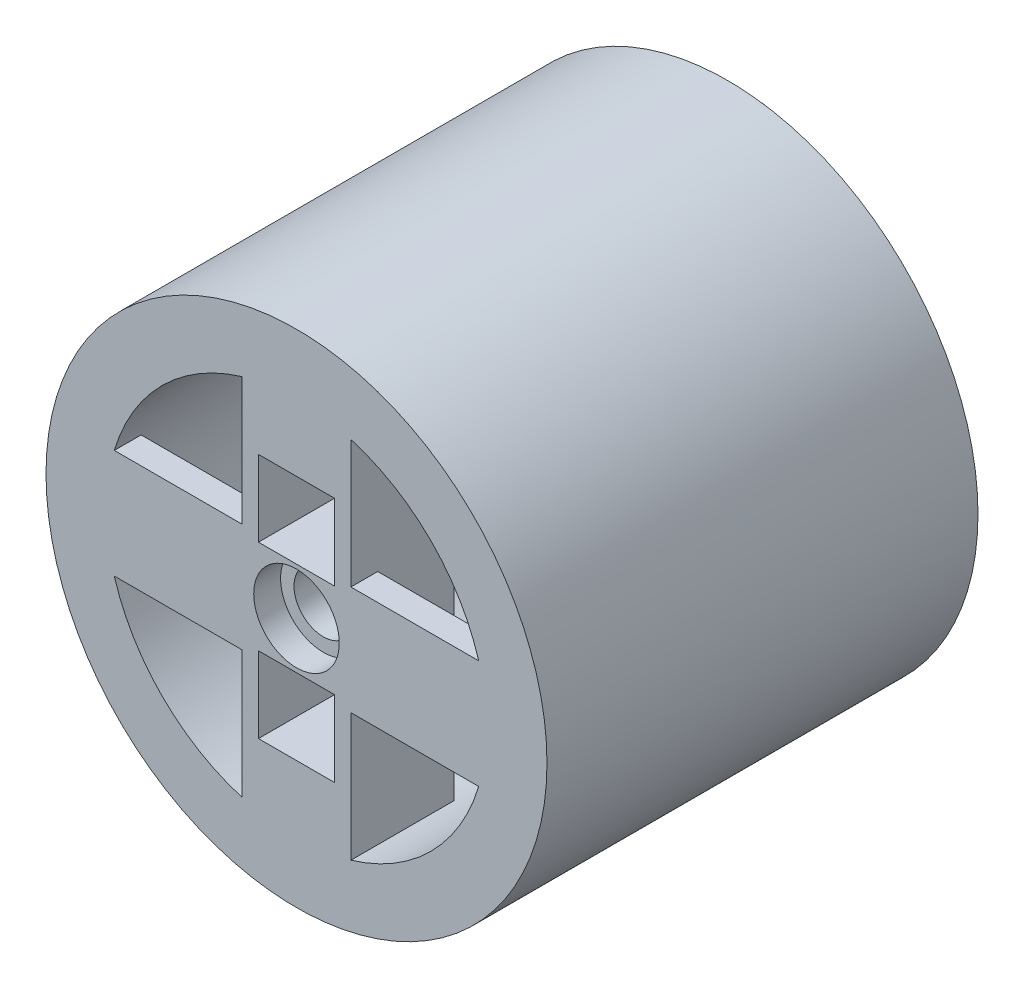
SolidWorks part; units mm, degrees
ref_plane "Front Plane" through (0, 0, 0) normal (0, 0, 1) x (1, 0, 0)
ref_plane "Top Plane" through (0, 0, 0) normal (0, 1, 0) x (1, 0, 0)
ref_plane "Right Plane" through (0, 0, 0) normal (1, 0, 0) x (0, 0, -1)
sketch "Sketch1" plane through (0, 0, 0) normal (0, 0, 1) x (1, 0, 0)
  line L0 (23.5, 0) -> (22.5, 0)
  line L1 (0, 25.15) -> (0, 22.5)
  line L3 (0, -22.5) -> (0, -29.64)
  line L4 (22.5, 0) -> (-22.5, 0)
  line L8 (28.3, 4.9) -> (23.5, 4.9)
  line L9 (28.3, 4.9) -> (28.3, -4.9)
  line L10 (28.3, -4.9) -> (23.5, -4.9)
  line L11 (23.5, 4.9) -> (23.5, -4.9)
  line L24 (-2.85, 27.85) -> (-2.85, 25.15)
  line L25 (-2.85, 27.85) -> (2.85, 27.85)
  line L26 (2.85, 27.85) -> (2.85, 25.15)
  line L27 (-2.85, 25.15) -> (2.85, 25.15)
  circle A0 centre (0, 0) radius 22.5
  circle A1 centre (0, 0) radius 29.64
  point P0 (0, 25.15)
  point P1 (23.5, 0)
  dimension "D3" = 5.7
  dimension "D1" = 1
  dimension "D2" = 2.65
  dimension "D4" = 2.7
extrude "Boss-Extrude1" add sketch "Sketch1" along normal blind 51 contours A1 L11 L8 L9 L10 L27 L24 L25 L26 A0 | L24 L27 L26 L25 | L8 L11 L10 L9 | L3 A1 L9 L10 L11 L0 A0 region at (-20.3658, 20.3658, 0) region at (0, 26.5, 0) region at (25.9, 0, 0)
extrude "Boss-Extrude2" add sketch "Sketch1<4>" against normal blind 1.5 contours L25 L26 L27 L24
sketch "Sketch1<4>" plane through (0, 0, 0) normal (0, 0, 1) x (1, 0, 0) same geometry as "Sketch1"
sketch "Sketch3" plane through (0, 0, 0) normal (0, 1, 0) x (1, 0, 0)
  line L0 (0, -26.5014) -> (0, 0)
pattern_circular "CirPattern2" count 3 over 360 about axis through (0, 0, 26.5014) along (0, 0, -1) of "Boss-Extrude2" reverse direction yes
sketch "Sketch4" plane through (0, 0, 51) normal (0, 0, 1) x (1, 0, 0)
  line L1 (6.4367, -24.2141) -> (-6.4367, -24.2141)
  line L2 (6.4367, -24.2141) -> (6.4367, 24.2141)
  line L3 (6.4367, 24.2141) -> (-6.4367, 24.2141)
  line L4 (-6.4367, -24.2141) -> (-6.4367, 24.2141)
  line L5 (6.4367, -24.2141) -> (-6.4367, 24.2141) construction
  line L6 (6.4367, 24.2141) -> (-6.4367, -24.2141) construction
  line L7 (-24.2141, 6.4367) -> (24.2141, 6.4367)
  line L8 (-24.2141, 6.4367) -> (-24.2141, -6.4367)
  line L9 (-24.2141, -6.4367) -> (24.2141, -6.4367)
  line L10 (24.2141, 6.4367) -> (24.2141, -6.4367)
  line L11 (-24.2141, 6.4367) -> (24.2141, -6.4367) construction
  line L12 (-24.2141, -6.4367) -> (24.2141, 6.4367) construction
  point P0 (0, 0)
  point P5 (0, 0)
  point P11 (6.4367, 24.2141)
  circle M5 centre (0, 0) radius 22.5
extrude "Boss-Extrude3" add sketch "Sketch4" against normal blind 3.175 contours L2 L9 L7 M5 | L9 L4 L2 M5 | L9 L10 L7 L8 | L2 L3 L4 L1 region at (0, -14.3154, 51) region at (14.3154, 0, 51)
sketch "Sketch7" plane through (0, 0, 51) normal (0, 0, 1) x (1, 0, 0)
  circle A0 centre (0, 0) radius 5.0625
extrude "Cut-Extrude2" cut sketch "Sketch7" against normal up to next and the other way through all
sketch "Sketch8" plane through (0, 0, 47.825) normal (0, 0, 1) x (1, 0, 0)
  line L0 (0, -3.475) -> (0, -24.0864)
  line L5 (6.4367, 24.0864) -> (-6.4367, 24.0864)
  line L6 (6.4367, 24.0864) -> (6.4367, -24.0864)
  line L11 (6.4367, -24.0864) -> (-6.4367, -24.0864)
  line L12 (-6.4367, 24.0864) -> (-6.4367, -24.0864)
  line L13 (6.4367, 24.0864) -> (-6.4367, -24.0864) construction
  line L14 (6.4367, -24.0864) -> (-6.4367, 24.0864) construction
  line L15 (6.4367, 6.4367) -> (6.4367, 21.5597) construction
  circle A1 centre (0, 0) radius 3.475
  point P0 (0, 0)
  dimension "D2" = 12.8734
extrude "Boss-Extrude4" add sketch "Sketch8" against normal blind 9 contours L5 L12 L11 L6 | A1
extrude "Cut-Extrude1" cut sketch "Sketch1<3>" along normal blind 23 contours L8 L11 L10 L9 region at (25.9, 0, 0)
sketch "Sketch1<3>" plane through (0, 0, 0) normal (0, 0, 1) x (1, 0, 0) same geometry as "Sketch1"
pattern_circular "CirPattern1" count 6 over 360 about axis through (0, 0, 26.5014) along (0, 0, -1) of "Cut-Extrude1" reverse direction yes
sketch "Sketch11" plane through (0, 0, 51) normal (0, 0, -1) x (-1, 0, 0)
  line L0 (0, 5.5625) -> (0, 5.0625)
  line L1 (-4.5, 14.5625) -> (4.5, 14.5625)
  line L2 (-4.5, 14.5625) -> (-4.5, 5.5625)
  line L3 (-4.5, 5.5625) -> (4.5, 5.5625)
  line L4 (4.5, 14.5625) -> (4.5, 5.5625)
  line L5 (-4.5, 14.5625) -> (4.5, 5.5625) construction
  line L6 (-4.5, 5.5625) -> (4.5, 14.5625) construction
  circle A0 centre (0, 0) radius 5.0625 construction
  point P0 (0, 10.0625)
  dimension "D1" = 9
extrude "Cut-Extrude21" cut sketch "Sketch11" along normal blind 29 contours L1 L4 L3 L2 region at (0, 10.0625, 51)
mirror "Mirror1" about plane through (0, 0, 0) normal (0, 1, 0) of "Cut-Extrude21"
